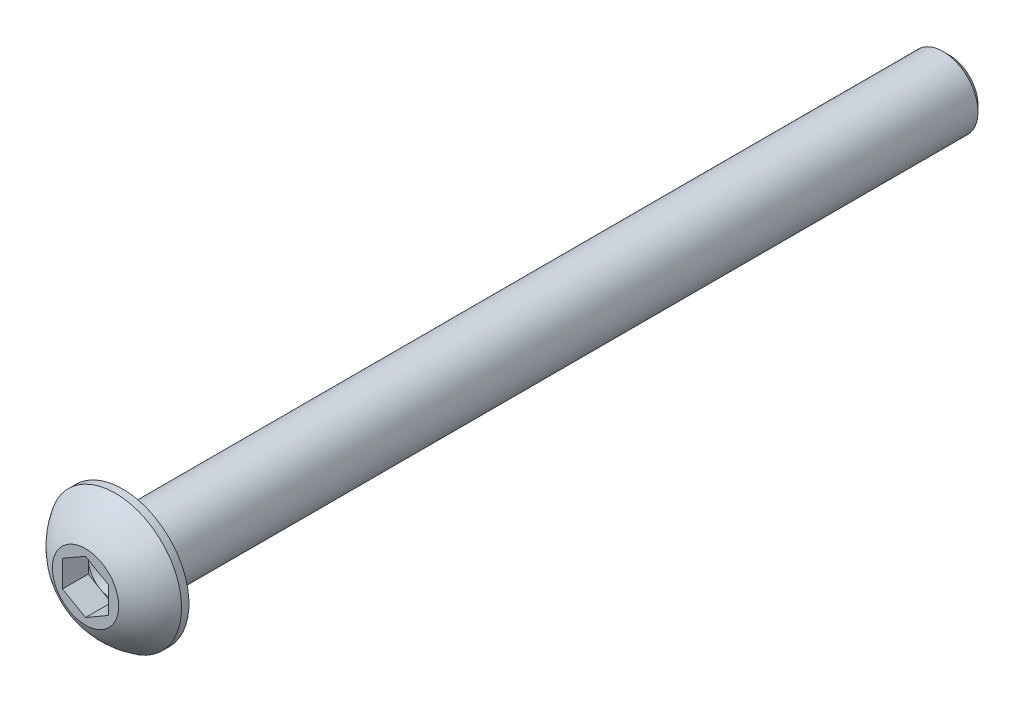
SolidWorks part; units mm, degrees
ref_plane "Front Plane" through (0, 0, 0) normal (0, 0, 1) x (1, 0, 0)
ref_plane "Top Plane" through (0, 0, 0) normal (0, 1, 0) x (1, 0, 0)
ref_plane "Right Plane" through (0, 0, 0) normal (1, 0, 0) x (0, 0, -1)
ref_plane "Plane1" through (0, 0, 0) normal (0, -1, 0) x (1, 0, 0)
sketch "Sketch1" plane through (0, 0, 0) normal (0, -1, 0) x (1, 0, 0)
  line L0 (2.2923, 0) -> (0, 0)
  line L1 (0, 0) -> (0, -2.5654)
  line L2 (0, -2.5654) -> (4.5847, -2.5654)
  line L3 (4.5847, -2.5654) -> (4.5847, -2.0574)
  line L4 (0, 0) -> (0, -2.5654) construction
  arc A0 (4.5847, -2.0574) -> (2.2923, 0) centre (0, -4.8599) ccw
  dimension "D1" = 5.3734
  dimension "D2" = 2.2923
  dimension "D3" = 4.5847
  dimension "D4" = 2.5654
revolve "Revolve1" add sketch "Sketch1" angle 360 about L4 reverse direction yes
sketch "Sketch2" plane through (0, 0, -2.5654) normal (0, 0, -1) x (-1, 0, 0)
  circle A0 centre (0, 0) radius 2.413
  dimension "D1" = 4.826
extrude "Boss-Extrude1" add sketch "Sketch2" along normal blind 57.15
sketch "Sketch3" plane through (0, 0, 0) normal (0, 0, 1) x (1, 0, 0)
  line L0 (1.5875, -0.9165) -> (1.5875, 0.9165)
  line L1 (1.5875, 0.9165) -> (0, 1.8331)
  line L2 (0, 1.8331) -> (-1.5875, 0.9165)
  line L3 (-1.5875, 0.9165) -> (-1.5875, -0.9165)
  line L4 (-1.5875, -0.9165) -> (0, -1.8331)
  line L5 (0, -1.8331) -> (1.5875, -0.9165)
  circle A0 centre (0, 0) radius 2.2923 construction
  dimension "D1" = 1.5875
  dimension "D2" = 1.5875
  dimension "D3" = 0.9165
  dimension "D4" = 1.8331
  dimension "D5" = 0.9165
  dimension "D6" = 1.8331
extrude "Cut-Extrude1" cut sketch "Sketch3" against normal blind 1.778
sketch "Sketch4" plane through (0, 0, 0) normal (0, -1, 0) x (1, 0, 0)
  line L0 (1.5875, -1.778) -> (0, -1.778)
  line L1 (0, -1.778) -> (0, -2.6945)
  line L2 (0, -2.6945) -> (1.5875, -1.778)
  line L3 (0, -1.778) -> (0, -2.6945) construction
  dimension "D1" = 1.5875
  dimension "D2" = 0.9165
revolve "Cut-Revolve1" cut sketch "Sketch4" angle 360 about L3 reverse direction yes
chamfer "Chamfer1" distance 0.4289 angle 45 1 edges at (-2.413, 0, -59.7154)
fillet "Fillet1" radius 0.381 1 edges at (-2.413, 0, -2.5654) tangent propagation no
